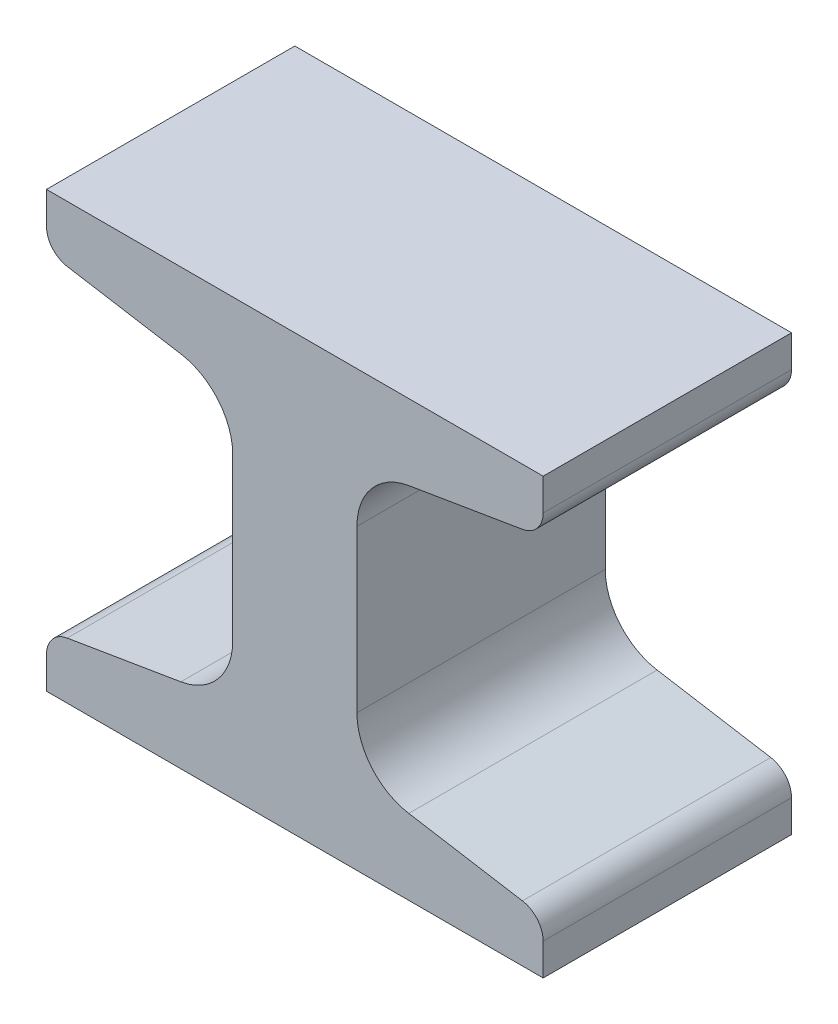
SolidWorks part; units mm, degrees
ref_plane "Plane1" through (0, 0, 0) normal (0, 0, 1) x (1, 0, 0)
ref_plane "Plane2" through (0, 0, 0) normal (0, 1, 0) x (-1, 0, 0)
ref_plane "Plane3" through (0, 0, 0) normal (1, 0, 0) x (0, 0, -1)
sketch "Sketch1" plane through (0, 0, 0) normal (0, 0, 1) x (1, 0, 0)
  line L0 (0, 0) -> (0, 3.2645)
  line L1 (2.1225, 5.77) -> (13.7437, 7.7064)
  line L2 (19.05, 13.97) -> (19.05, 30.48)
  line L3 (13.7437, 36.7436) -> (2.1225, 38.68)
  line L4 (0, 41.1855) -> (0, 44.45)
  line L5 (0, 44.45) -> (50.8, 44.45)
  line L6 (50.8, 44.45) -> (50.8, 41.1855)
  line L7 (48.6775, 38.68) -> (37.0563, 36.7436)
  line L8 (31.75, 30.48) -> (31.75, 13.97)
  line L9 (37.0563, 7.7064) -> (48.6775, 5.77)
  line L10 (50.8, 3.2645) -> (50.8, 0)
  line L11 (50.8, 0) -> (0, 0)
  line L12 (15.6984, 0) -> (-15.6984, 0) construction
  line L13 (0, -13.7361) -> (0, 13.7361) construction
  arc A0 (13.7437, 7.7064) -> (19.05, 13.97) centre (12.7, 13.97) ccw
  arc A1 (19.05, 30.48) -> (13.7437, 36.7436) centre (12.7, 30.48) ccw
  arc A2 (37.0563, 36.7436) -> (31.75, 30.48) centre (38.1, 30.48) ccw
  arc A3 (31.75, 13.97) -> (37.0563, 7.7064) centre (38.1, 13.97) ccw
  arc A4 (48.6775, 38.68) -> (50.8, 41.1855) centre (48.26, 41.1855) ccw
  arc A5 (2.1225, 38.68) -> (0, 41.1855) centre (2.54, 41.1855) cw
  arc A6 (48.6775, 5.77) -> (50.8, 3.2645) centre (48.26, 3.2645) cw
  arc A7 (2.1225, 5.77) -> (0, 3.2645) centre (2.54, 3.2645) ccw
  dimension "D7" = 9.46
  dimension "RI" = 6.35
  dimension "RA" = 2.54
  dimension "BF" = 50.8
  dimension "D6" = 9.46
  dimension "DEPTH" = 44.45
  dimension "TW" = 12.7
  dimension "D1" = 16.51
extrude "BaseAlumBeam" add sketch "Sketch1" along normal mid plane 25.4
